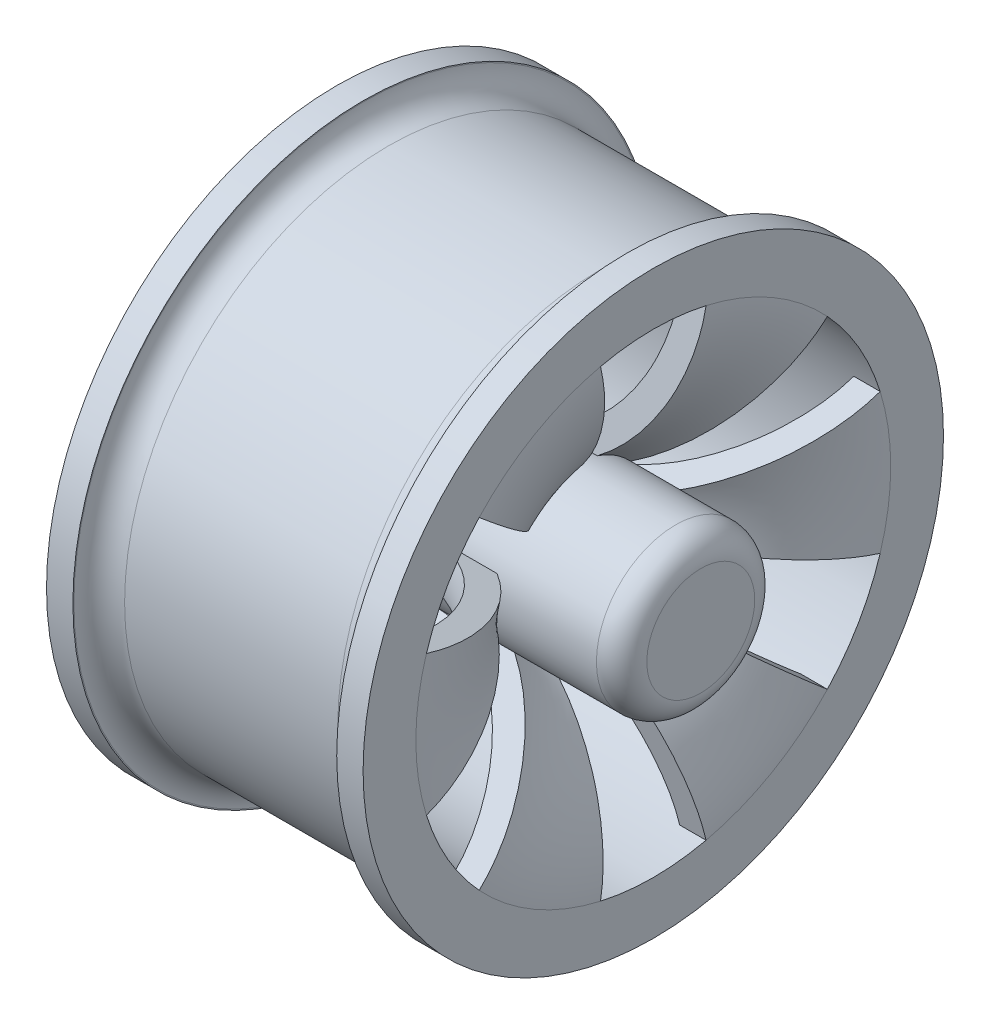
SolidWorks part; units mm, degrees
ref_plane "Front Plane" through (0, 0, 0) normal (0, 0, 1) x (1, 0, 0)
ref_plane "Top Plane" through (0, 0, 0) normal (0, 1, 0) x (1, 0, 0)
ref_plane "Right Plane" through (0, 0, 0) normal (1, 0, 0) x (0, 0, -1)
sketch "Sketch1" plane through (0, 0, 0) normal (0, 0, 1) x (1, 0, 0)
  line L0 (0, 0) -> (137.1685, 0) construction
  line L1 (0, 0) -> (0, 94.2754) construction
  line L2 (-38.1, 57.15) -> (31.75, 57.15)
  line L3 (38.1, 57.15) -> (38.1, 69.85)
  line L4 (38.1, 69.85) -> (31.75, 69.85)
  line L5 (31.75, 69.85) -> (31.75, 69.596)
  line L6 (25.654, 63.5) -> (-25.654, 63.5)
  line L8 (-38.1, 57.15) -> (-38.1, 69.85)
  line L9 (-38.1, 69.85) -> (-31.75, 69.85)
  line L10 (0, 12.7) -> (0, 19.0502)
  line L11 (-31.75, 69.85) -> (-31.75, 69.596)
  arc A0 (31.75, 69.596) -> (25.654, 63.5) centre (25.654, 69.596) cw
  arc A1 (-31.75, 69.596) -> (-25.654, 63.5) centre (-25.654, 69.596) ccw
  spline S0 degree 3 poles (38.1, 57.15) (38.1, 37.4566) (22.4711, 12.866) (0, 12.7) knots 0 0 0 0 1 1 1 1
  spline S1 degree 1 poles (31.75, 57.15) (-0.0469, 19.0498) knots 0 0 1 1 construction
  spline S2 degree 3 poles (31.75, 57.15) (31.75, 56.6324) (31.7247, 55.6073) (31.5721, 53.4812) (31.1901, 50.7555) (30.4293, 47.4118) (29.0235, 42.9331) (26.5609, 37.4238) (22.6049, 31.3518) (17.8118, 26.1818) (13.2772, 22.8836) (9.4043, 20.9611) (6.3858, 19.8958) (3.7702, 19.3374) (1.617, 19.1001) (0.5052, 19.0539) (-0.0469, 19.0498) knots 0 0 0 0 0.03125 0.0625 0.125 0.1875 0.25 0.375 0.5 0.625 0.75 0.8125 0.875 0.9375 0.96875 1 1 1 1 only from (31.75, 57.15) to (0, 19.0502)
  point P13 (0, 57.15)
  point P18 (0, 63.5)
  dimension "D6" = 6.096
  dimension "D1" = 38.1
  dimension "D2" = 12.7
  dimension "D3" = 6.35
  dimension "D4" = 6.35
  dimension "D5" = 63.5
  dimension "D7" = 12.7
  dimension "D8" = 25.4
  dimension "D9" = 6.35
revolve "Revolve1" add sketch "Sketch1" angle 360 about L0
sketch "Sketch2" plane through (-38.1, 0, 0) normal (-1, 0, 0) x (0, 0, 1)
  circle A0 centre (0, 0) radius 12.7 construction
  circle A1 centre (0, 0) radius 12.7
  circle A2 centre (0, 0) radius 19.0502 construction
  circle A3 centre (0, 0) radius 19.0502
extrude "Boss-Extrude1" add sketch "Sketch2" against normal blind 82.55
sketch "Sketch5" plane through (38.1, 0, 0) normal (1, 0, 0) x (0, 0, -1)
  line L0 (-5.9144, 18.1088) -> (-4.2334, 18.5739)
  line L1 (-4.2334, 18.5739) -> (-12.7, 55.721)
  line L4 (12.7, 55.721) -> (5.9144, 18.1088)
  circle A0 centre (0, 0) radius 19.0502 construction
  circle A1 centre (0, 0) radius 69.85
  circle A2 centre (0, 0) radius 69.85
  circle A3 centre (0, 0) radius 19.0502
  circle A4 centre (0, 0) radius 57.15 construction
  circle A5 centre (0, 0) radius 57.15
  circle M9 centre (0, 0) radius 57.15
  dimension "D2" = 25.4
  dimension "D1" = 0
extrude "Cut-Extrude1" cut sketch "Sketch5" against normal through all contours A3 L4 L1 M9 region at (38.1, 40.4395, -0.3695)
pattern_circular "CirPattern1" count 6 over 360 about axis through (44.45, 0, 0) along (-1, 0, 0) of "Cut-Extrude1"
sketch "Sketch7" plane through (44.45, 0, 0) normal (1, 0, 0) x (0, 0, -1)
  circle A0 centre (0, 0) radius 19.0502 construction
  circle A1 centre (0, 0) radius 19.0502
extrude "Boss-Extrude2" add sketch "Sketch7" along normal blind 5.08
fillet "Fillet2" radius 6.0706 1 edges at (49.53, 0, -19.0502)
